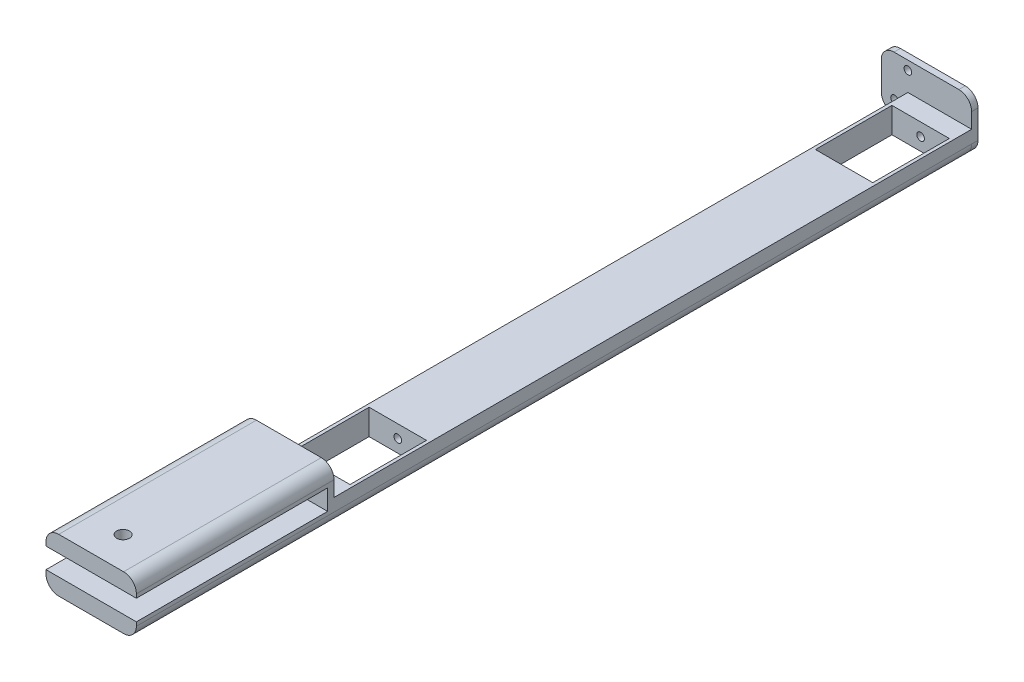
SolidWorks part; units mm, degrees
material "Alloy Steel"
ref_plane "Front Plane" through (0, 0, 0) normal (0, 0, 1) x (1, 0, 0)
ref_plane "Top Plane" through (0, 0, 0) normal (0, 1, 0) x (1, 0, 0)
ref_plane "Right Plane" through (0, 0, 0) normal (1, 0, 0) x (0, 0, -1)
sketch "Sketch1" plane through (0, 0, 0) normal (0, 0, 1) x (1, 0, 0)
  line L1 (250, 100) -> (-250, 100)
  line L2 (250, 100) -> (250, -100)
  line L3 (250, -100) -> (-250, -100)
  line L4 (-250, 100) -> (-250, -100)
  line L5 (250, 100) -> (-250, -100) construction
  line L6 (250, -100) -> (-250, 100) construction
  point P0 (0, 0)
  dimension "D1" = 500
  dimension "D2" = 200
extrude "Boss-Extrude1" add sketch "Sketch1" along normal blind 5000
ref_plane "Plane1" through (0, 0, 4850) normal (0, 0, 1) x (1, 0, 0)
sketch "Sketch2" plane through (0, 0, 4850) normal (0, 0, 1) x (1, 0, 0)
  line L0 (-250, -100) -> (250, -100) construction
  line L1 (225, 100) -> (-225, 100)
  line L2 (225, 100) -> (225, -100)
  line L3 (225, -100) -> (-225, -100)
  line L4 (-225, 100) -> (-225, -100)
  line L5 (225, 100) -> (-225, -100) construction
  line L6 (225, -100) -> (-225, 100) construction
  point P0 (0, 0)
  dimension "D1" = 450
extrude "Cut-Extrude1" cut sketch "Sketch2" against normal blind 600
ref_axis "Axis1" through (250, 100, 2500) along (-1, 0, 0)
ref_plane "Plane2" through (0, 0, 2500) normal (0, 0, 1) x (1, 0, 0)
mirror "Mirror1" about plane through (0, 0, 2500) normal (0, 0, 1) of "Cut-Extrude1"
ref_plane "Plane3" through (0, 0, 5050) normal (0, 0, 1) x (1, 0, 0)
sketch "Sketch3" plane through (0, 0, 5000) normal (0, 0, 1) x (1, 0, 0)
  line L0 (-250, -100) -> (-250, 455.1676)
  line L2 (458.7018, -100) -> (-250, -100)
  line L4 (-250, 455.1676) -> (458.7018, 455.1676)
  line L5 (458.7018, 455.1676) -> (458.7018, -100)
  line L6 (250, 100) -> (-250, 100) construction
  line L7 (-250, 455.1676) -> (458.7018, 455.1676)
  line L8 (-250, 455.1676) -> (-250, 320)
  line L9 (-250, 320) -> (458.7018, 320)
  line L10 (458.7018, 455.1676) -> (458.7018, 320)
  dimension "D1" = 220
sketch "Sketch5" plane through (0, 0, 4850) normal (0, 0, -1) x (-1, 0, 0)
  circle A0 centre (0, 0) radius 30
  dimension "D1" = 60
extrude "Cut-Extrude3" cut sketch "Sketch5" against normal blind 300 and the other way blind 5000
scale "Scale2" scale about centroid uniform scaling yes scale factor 0.1
ref_plane "Plane4" through (0, 0, 2500) normal (0, 0, 1) x (1, 0, 0)
sketch "Sketch13" plane through (0, 0, 2750) normal (0, 0, 1) x (1, 0, 0)
  line L1 (25, -10) -> (-45.87, -10)
  line L2 (25, -10) -> (25, 32)
  line L3 (25, 32) -> (-45.87, 32)
  line L4 (-45.87, -10) -> (-45.87, 32)
  dimension "D1" = 70.87
  dimension "D2" = 42
extrude "Boss-Extrude7" add sketch "Sketch13" along normal blind 5
sketch "Sketch14" plane through (0, 0, 2755) normal (0, 0, 1) x (1, 0, 0)
  line L0 (-25, 10) -> (-45.87, -10) construction
  circle A0 centre (-35.435, 0) radius 3
  circle A1 centre (-25, 25) radius 3
  dimension "D1" = 6
  dimension "D2" = 6
  dimension "D3" = 15
extrude "Cut-Extrude8" cut sketch "Sketch14" against normal through all both
fillet "Fillet9" radius 10 4 edges at (-45.87, 32, 2752.5) (-45.87, -10, 2752.5) (25, -10, 2502.5) (25, 32, 2752.5)
sketch "Sketch15" plane through (0, 0, 2755) normal (0, 0, 1) x (1, 0, 0)
  line L0 (-45.87, 19) -> (25, 19)
  line L1 (-45.87, 22) -> (-45.87, 0) construction
  line L2 (25, 0) -> (25, 22) construction
  line L3 (-45.87, 19) -> (-45.87, 22)
  line L4 (25, 19) -> (25, 22)
  line L5 (-35.87, 32) -> (15, 32)
  line L6 (-45.87, 11) -> (25, 11) construction
  line L7 (25, 3) -> (25, 0)
  line L8 (-45.87, 3) -> (25, 3)
  line L9 (-45.87, 3) -> (-45.87, 0)
  line L10 (-35.87, -10) -> (15, -10)
  arc A0 (-35.87, 32) -> (-45.87, 22) centre (-35.87, 22) ccw
  arc A1 (25, 22) -> (15, 32) centre (15, 22) ccw
  arc A2 (-35.87, -10) -> (-45.87, 0) centre (-35.87, 0) cw
  arc A3 (25, 0) -> (15, -10) centre (15, 0) cw
  dimension "D1" = 13
extrude "Boss-Extrude8" add sketch "Sketch15" along normal blind 150 and the other way blind 1
sketch "Sketch16" plane through (0, 32, 0) normal (0, 1, 0) x (1, 0, 0)
  line L0 (15, -2905) -> (-35.87, -2905) construction
  circle A0 centre (-10.435, -2880) radius 5
  dimension "D1" = 10
  dimension "D2" = 25
extrude "Cut-Extrude9" cut sketch "Sketch16" against normal through all both
mirror "Mirror9" about plane through (0, 0, 2500) normal (0, 0, 1) of "Boss-Extrude7"
sketch "Sketch17" plane through (0, 0, 2245) normal (0, 0, -1) x (-1, 0, 0)
  circle A0 centre (25, 25) radius 3
  circle A1 centre (35.435, 0) radius 3
extrude "Cut-Extrude10" cut sketch "Sketch17" against normal blind 5
fillet "Fillet10" radius 10 4 edges at (-45.87, 32, 2247.5) (-45.87, -10, 2247.5) (25, -10, 2247.5) (25, 32, 2247.5)
sketch "Sketch18" plane through (0, 0, 2250) normal (0, 0, 1) x (1, 0, 0)
  circle A1 centre (0, 0) radius 3
  circle A2 centre (0, 0) radius 3
  dimension "D1" = 0
extrude "Cut-Extrude11" cut sketch "Sketch18" against normal blind 10
